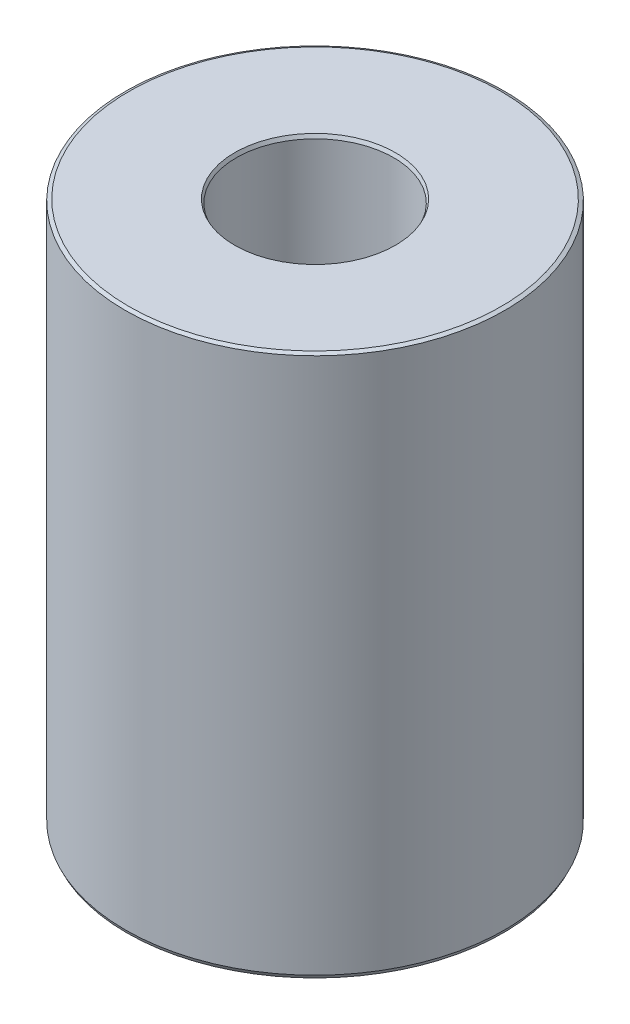
SolidWorks part; units mm, degrees
ref_plane "Front Plane" through (0, 0, 0) normal (0, 0, 1) x (1, 0, 0)
ref_plane "Top Plane" through (0, 0, 0) normal (0, 1, 0) x (1, 0, 0)
ref_plane "Right Plane" through (0, 0, 0) normal (1, 0, 0) x (0, 0, -1)
sketch "Sketch1" plane through (0, 0, 0) normal (0, 1, 0) x (1, 0, 0)
  circle A0 centre (0, 0) radius 32.5
  dimension "SLEEVE_OD" = 65
extrude "Boss-Extrude1" add sketch "Sketch1" along normal blind 92.769
sketch "Sketch2" plane through (0, 0, 0) normal (0, 1, 0) x (1, 0, 0)
  circle A0 centre (0, 0) radius 13.4766
  dimension "BORE_D" = 26.9531
extrude "Cut-Extrude1" cut sketch "Sketch2" along normal through all
chamfer "Chamfer1" distance 0.2851 angle 64.926 4 edges at (0, 92.769, 13.4766) (0, 0, 13.4766) (0, 0, 32.5) (0, 92.769, 32.5) first distance on face at (0, 92.769, 13.4766) first distance on face at (0, 0, 13.4766) first distance on face at (0, 92.769, 32.5)
